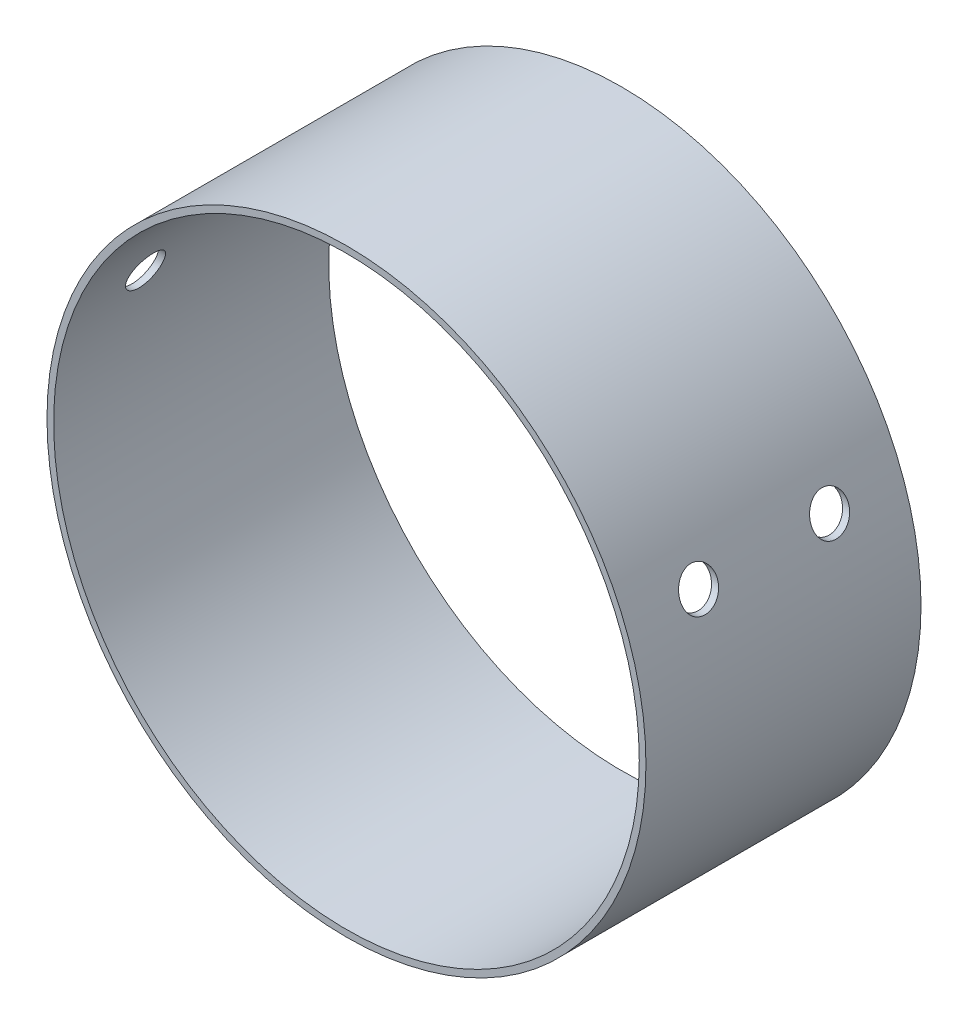
SolidWorks part; units mm, degrees
material "E-Glass Fiber"
ref_plane "Front Plane" through (0, 0, 0) normal (0, 0, 1) x (1, 0, 0)
ref_plane "Top Plane" through (0, 0, 0) normal (0, 1, 0) x (1, 0, 0)
ref_plane "Right Plane" through (0, 0, 0) normal (1, 0, 0) x (0, 0, -1)
sketch "Sketch1" plane through (0, 0, 0) normal (0, 0, 1) x (1, 0, 0)
  circle A0 centre (0, 0) radius 50.8
  circle A1 centre (0, 0) radius 49.6697
  dimension "D1" = 101.6
  dimension "D2" = 99.3394
extrude "Boss-Extrude1" add sketch "Sketch1" along normal mid plane 46.6598
sketch "Sketch2" plane through (0, 0, 0) normal (1, 0, 0) x (0, 0, -1)
  line L0 (0, 0) -> (0, 17.9375) construction
  line L1 (0, 17.9375) -> (11.1125, 17.9375) construction
  line L2 (0, 17.9375) -> (-11.1125, 17.9375) construction
  line L4 (0, 55.88) -> (0, -55.88) construction
  circle A0 centre (-11.1125, 17.9375) radius 3.175
  circle A1 centre (11.1125, 17.9375) radius 3.175
  dimension "D3" = 6.35
  dimension "D1" = 17.9375
  dimension "D2" = 22.225
extrude "Cut-Extrude1" cut sketch "Sketch2" against normal through all and the other way through all
